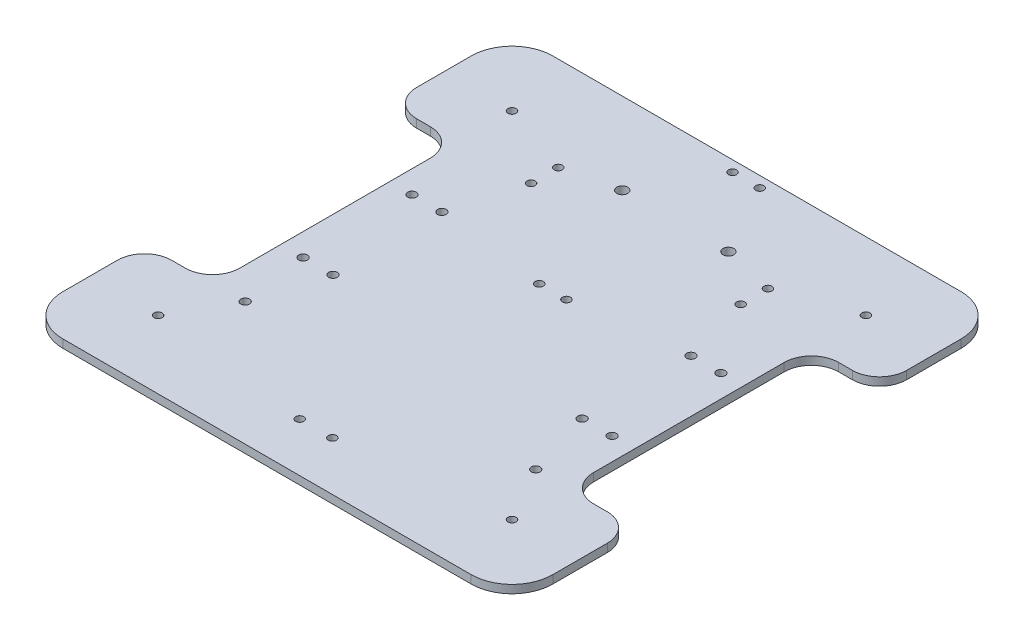
SolidWorks part; units mm, degrees
ref_plane "Спереди" through (0, 0, 0) normal (0, 0, 1) x (1, 0, 0)
ref_plane "Сверху" through (0, 0, 0) normal (0, 1, 0) x (1, 0, 0)
ref_plane "Справа" through (0, 0, 0) normal (1, 0, 0) x (0, 0, -1)
sketch "Sketch1" plane through (0, 0, 0) normal (0, 1, 0) x (1, 0, 0)
  line L1 (-90, 90) -> (90, 90)
  line L2 (-90, 90) -> (-90, -90)
  line L3 (-90, -90) -> (90, -90)
  line L4 (90, 90) -> (90, -90)
  line L5 (-90, 90) -> (90, -90) construction
  line L6 (-90, -90) -> (90, 90) construction
  point P0 (0, 0)
  dimension "D1" = 180
  dimension "D2" = 180
extrude "Boss-Extrude1" add sketch "Sketch1" along normal blind 3
fillet "Fillet1" radius 15 4 edges at (-90, 1.5, -90) (90, 1.5, -90) (-90, 1.5, 90) (90, 1.5, 90)
sketch "Sketch2" plane through (0, 3, 0) normal (0, 1, 0) x (1, 0, 0)
  line L0 (0, 0) -> (-77.5, 0) construction
  line L1 (2.75, 0) -> (-2.75, 0) construction
  line L2 (-90, 75) -> (-90, -75) construction
  line L3 (-90, 45) -> (-65, 45)
  line L4 (-90, 45) -> (-90, -45)
  line L5 (-90, -45) -> (-65, -45)
  line L6 (-65, 45) -> (-65, -45)
  line L7 (-90, 45) -> (-65, -45) construction
  line L8 (-90, -45) -> (-65, 45) construction
  line L9 (0, 0) -> (0, 45) construction
  line L10 (90, -45) -> (65, 45) construction
  line L11 (90, 45) -> (65, -45) construction
  line L12 (65, 45) -> (65, -45)
  line L13 (90, -45) -> (65, -45)
  line L14 (90, 45) -> (90, -45)
  line L15 (90, 45) -> (65, 45)
  circle A0 centre (-56.75, 20) radius 1.6
  circle A1 centre (-45.75, 20) radius 1.6
  circle A2 centre (-56.75, -20) radius 1.6
  circle A3 centre (-45.75, -20) radius 1.6
  circle A4 centre (45.75, 20) radius 1.6
  circle A5 centre (56.75, 20) radius 1.6
  circle A6 centre (45.75, -20) radius 1.6
  circle A7 centre (56.75, -20) radius 1.6
  dimension "D1" = 25
  dimension "D2" = 90
extrude "Cut-Extrude2" cut sketch "Sketch2" against normal through all
fillet "Fillet2" radius 10 8 edges at (-65, 1.5, 45) (-65, 1.5, -45) (65, 1.5, -45) (65, 1.5, 45) (90, 1.5, -45) (90, 1.5, 45) (-90, 1.5, 45) (-90, 1.5, -45)
hole_wizard "Диаметр отверстия Ø3.0 (3)1" positions "Эскиз2" profile "Эскиз1" hole size "Ø3.0" standard "Ansi Metric" end condition up to next
sketch "Эскиз2" plane through (0, 3, 0) normal (0, 1, 0) x (1, 0, 0)
  line L7 (-65, -65) -> (-65, 65) construction
  line L9 (65, 65) -> (65, -65) construction
  line L11 (-90, 65) -> (-65, 65) construction
  line L12 (-90, 75) -> (-90, 55) construction
  line L13 (-65, 65) -> (65, 65) construction
  line L14 (65, 65) -> (90, 65) construction
  line L15 (90, 55) -> (90, 75) construction
  line L17 (90, -65) -> (65, -65) construction
  line L18 (90, -75) -> (90, -55) construction
  line L19 (65, -65) -> (-65, -65) construction
  line L20 (-65, -65) -> (-90, -65) construction
  line L21 (-90, -55) -> (-90, -75) construction
  line L22 (-65, 65) -> (-65, 90) construction
  line L23 (75, 90) -> (-75, 90) construction
  point P15 (-65, -65)
  point P16 (-65, 65)
  point P19 (65, 65)
  point P20 (65, -65)
sketch "Эскиз1" plane through (-65, 3, 65) normal (1, 0, 0) x (0, 0, 1)
  line L0 (0, 0) -> (0, 3)
  line L1 (0, 3) -> (1.5, 3)
  line L2 (1.5, 3) -> (1.5, 0)
  line L5 (1.5, 0) -> (0, 0)
  line L11 (0, -6.35) -> (0, 107.95) construction
  dimension "Диаметр сквозного отверстия" = 3
  dimension "Глубина сквозного отверстия" = 3
hole_wizard "Диаметр отверстия Ø3.0 (3)2" positions "Эскиз4" profile "Эскиз3" hole size "Ø3.0" standard "Ansi Metric" end condition up to next
sketch "Эскиз4" plane through (0, 3, 0) normal (0, 1, 0) x (1, 0, 0)
  line L0 (90, 65) -> (38.5, 65) construction
  line L1 (90, 55) -> (90, 75) construction
  line L2 (38.5, 65) -> (-38.5, 65) construction
  line L3 (-38.5, 65) -> (-90, 65) construction
  line L4 (-90, 75) -> (-90, 55) construction
  line L12 (-38.5, 15) -> (-5, 15) construction
  line L13 (-5, 15) -> (5, 15) construction
  line L14 (5, 15) -> (38.5, 15) construction
  line L16 (38.5, 86) -> (5, 86) construction
  line L17 (5, 86) -> (-5, 86) construction
  line L18 (-5, 86) -> (-38.5, 86) construction
  line L20 (38.5, 15) -> (38.5, 45.5) construction
  line L21 (38.5, 45.5) -> (38.5, 55.5) construction
  line L22 (38.5, 55.5) -> (38.5, 86) construction
  line L24 (-38.5, 86) -> (-38.5, 55.5) construction
  line L25 (-38.5, 55.5) -> (-38.5, 45.5) construction
  line L26 (-38.5, 45.5) -> (-38.5, 15) construction
  line L28 (75, 90) -> (-75, 90) construction
  point P63 (-5, 15)
  point P66 (-38.5, 45.5)
  point P69 (-38.5, 55.5)
  point P72 (5, 15)
  point P75 (38.5, 45.5)
  point P78 (38.5, 55.5)
  point P81 (5, 86)
  point P84 (-5, 86)
  dimension "D1" = 10
  dimension "D2" = 71
  dimension "D3" = 77
  dimension "D4" = 4
sketch "Эскиз3" plane through (-5, 3, -15) normal (1, 0, 0) x (0, 0, 1)
  line L0 (0, 0) -> (0, 3)
  line L1 (0, 3) -> (1.5, 3)
  line L2 (1.5, 3) -> (1.5, 0)
  line L5 (1.5, 0) -> (0, 0)
  line L11 (0, -6.35) -> (0, 107.95) construction
  dimension "Диаметр сквозного отверстия" = 3
  dimension "Глубина сквозного отверстия" = 3
hole_wizard "Диаметр отверстия Ø4.0 (4)1" positions "Эскиз6" profile "Эскиз5" hole size "Ø4.0" standard "Ansi Metric" end condition up to next
sketch "Эскиз6" plane through (0, 3, 0) normal (0, 1, 0) x (1, 0, 0)
  line L0 (0, 90) -> (0, 60) construction
  line L1 (75, 90) -> (-75, 90) construction
  line L2 (0, 60) -> (0, -90) construction
  line L3 (-75, -90) -> (75, -90) construction
  line L5 (-19.5, 60) -> (19.5, 60) construction
  point P1 (-19.5, 60)
  point P20 (19.5, 60)
  dimension "D1" = 39
  dimension "D2" = 30
sketch "Эскиз5" plane through (-19.5, 3, -60) normal (1, 0, 0) x (0, 0, 1)
  line L0 (0, 0) -> (0, 3)
  line L1 (0, 3) -> (2, 3)
  line L2 (2, 3) -> (2, 0)
  line L5 (2, 0) -> (0, 0)
  line L11 (0, -6.35) -> (0, 107.95) construction
  dimension "Диаметр сквозного отверстия" = 4
  dimension "Глубина сквозного отверстия" = 3
sketch "Sketch3" plane through (0, 3, 0) normal (0, 1, 0) x (1, 0, 0)
  line L0 (0, -90) -> (0, -72) construction
  line L1 (-75, -90) -> (75, -90) construction
  line L2 (0, -72) -> (-6, -72) construction
  circle A0 centre (-6, -72) radius 1.5
  circle A1 centre (6, -72) radius 1.5
  circle A2 centre (53.3716, -44.65) radius 1.6
  circle A3 centre (-53.3716, -44.65) radius 1.6
  arc A4 (-52.7899, -46.1405) -> (-54.9533, -44.8915) centre (-53.3716, -44.65) ccw construction
  arc A5 (54.9533, -44.8915) -> (52.7899, -46.1405) centre (53.3716, -44.65) ccw construction
  dimension "D2" = 3
  dimension "D1" = 18
  dimension "D3" = 12
extrude "Cut-Extrude3" cut sketch "Sketch3" against normal through all
